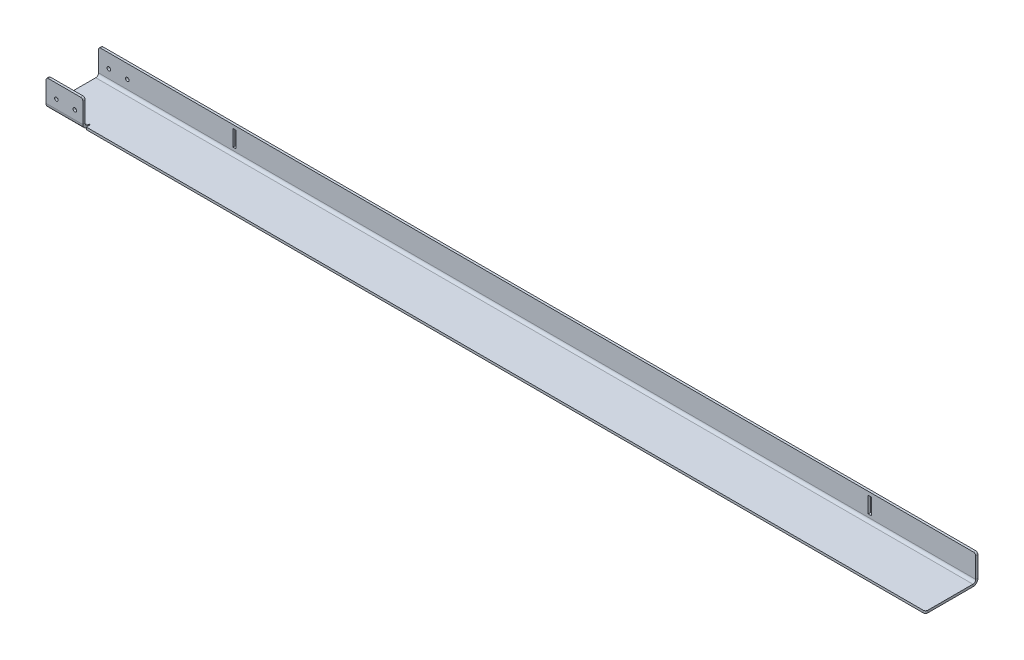
SolidWorks part; units mm, degrees
note: The reader was unsure of these and kept them because the rebuilt part matched: flange length of "Edge-Flange1", "Edge-Flange2"; thickness of "Edge-Flange1", "Edge-Flange2".
material "5052-H32"
ref_plane "Front Plane" through (0, 0, 0) normal (0, 0, 1) x (1, 0, 0)
ref_plane "Top Plane" through (0, 0, 0) normal (0, 1, 0) x (1, 0, 0)
ref_plane "Right Plane" through (0, 0, 0) normal (1, 0, 0) x (0, 0, -1)
sketch "Sketch1" plane through (0, 0, 0) normal (0, 1, 0) x (1, 0, 0)
  line L5 (-604.8375, -72.39) -> (604.8375, -72.39)
  line L6 (-604.8375, -72.39) -> (-604.8375, 0)
  line L7 (-604.8375, 0) -> (604.8375, 0)
  line L8 (604.8375, -72.39) -> (604.8375, 0)
  point P4 (0, 0)
  dimension "D1" = 1209.675
  dimension "D2" = 72.39
base flange "Base-Flange1" sketch "Sketch1" thickness 3.175 reverse thickness direction yes parameters "D1"=3.81
edge flange "Edge-Flange1" sketch "Sketch8" flange angle 90 flange length 38.1 flange position material inside bend radius 3.81 thickness 3.175 relief rectangular parameters "D6"=10
sketch "Sketch8" plane through (0, 3.175, 0) normal (0, 0, -1) x (-1, 0, 0)
  line L2 (604.8375, 0) -> (604.8375, 34.925)
  line L3 (604.8375, 34.925) -> (-604.8375, 34.925)
  line L4 (-604.8375, 34.925) -> (-604.8375, 0)
  line L7 (-604.8375, 0) -> (604.8375, 0) construction
  line L8 (-604.8375, 0) -> (604.8375, 0)
bend "EdgeBend1" bend radius 3.81 bend angle 90 parameters "D5"=1
sketch "Sketch9" plane through (0, 0, 0) normal (0, -1, 0) x (-1, 0, 0)
  line L0 (-604.8375, -72.39) -> (-604.8375, -6.985) construction
  line L2 (-604.8375, 0) -> (604.8375, 0) construction
  circle A0 centre (-364.3313, -38.1) radius 21.717
  circle A2 centre (116.6787, -38.1) radius 21.717
  dimension "D1" = 38.1
  dimension "D4" = 43.434
  dimension "D2" = 240.5062
  dimension "D3" = 481.01
extrude "Cut-Extrude1" [suppressed] cut sketch "Sketch9" against normal through all
sketch "Sketch10" plane through (0, 0, 0) normal (0, 0, -1) x (-1, 0, 0)
  line L0 (604.8375, 6.985) -> (604.8375, 38.1) construction
  line L1 (415.3535, 33.3375) -> (419.5445, 33.3375)
  line L2 (415.3535, 33.3375) -> (415.3535, 11.1125)
  line L3 (415.3535, 11.1125) -> (419.5445, 11.1125)
  line L4 (419.5445, 33.3375) -> (419.5445, 11.1125)
  line L5 (604.8375, 38.1) -> (-604.8375, 38.1) construction
  dimension "D1" = 185.293
  dimension "D2" = 4.191
  dimension "D3" = 22.225
  dimension "D4" = 4.7625
extrude "Cut-Extrude2" cut sketch "Sketch10" against normal through all normal cut yes
edge flange "Edge-Flange2" sketch "Sketch15" flange angle 90 flange length 38.1 flange position material outside bend radius 3.81 thickness 3.175 relief rectangular parameters "D6"=10
sketch "Sketch15" plane through (0, 3.175, 72.39) normal (0, 0, -1) x (-1, 0, 0)
  line L3 (554.0375, 34.925) -> (604.8375, 34.925)
  line L4 (604.8375, 34.925) -> (604.8375, 0)
  line L5 (604.8375, 0) -> (-604.8375, 0) construction
  line L6 (604.8375, 0) -> (554.0375, 0)
  line L7 (554.0375, 34.925) -> (554.0375, 0)
  dimension "D1" = 50.8
bend "EdgeBend2" bend radius 3.81 bend angle 90 parameters "D5"=2
hole_wizard "#10 (0.1935) Diameter Hole1" positions "Sketch16" profile "Sketch17" hole size "#10" standard "ANSI Inch" end condition through all
sketch "Sketch16" plane through (0, 0, 75.565) normal (0, 0, 1) x (1, 0, 0)
  line L0 (-554.0375, 0) -> (-604.8375, 0) construction
  line L1 (-554.0375, 38.1) -> (-554.0375, 6.985) construction
  point P0 (-565.15, 19.05)
  point P2 (-590.55, 19.05)
  dimension "D1" = 19.05
  dimension "D2" = 11.1125
  dimension "D3" = 25.4
sketch "Sketch17" plane through (-565.15, 19.05, 75.565) normal (1, 0, 0) x (0, -1, 0)
  line L0 (0, 0) -> (0, 75.565)
  line L1 (0, 75.565) -> (2.4574, 75.565)
  line L2 (2.4574, 75.565) -> (2.4574, 0)
  line L5 (2.4574, 0) -> (0, 0)
  line L11 (0, -6.35) -> (0, 107.95) construction
  dimension "Thru Hole Dia." = 4.9149
  dimension "Thru Hole Depth" = 75.565
fillet "Fillet1" radius 3.175 5 edges at (604.8375, 38.1, 1.5875) (604.8375, 1.5875, 72.39) (-604.8375, 38.1, 1.5875) (-604.8375, 38.1, 73.9775) (-554.0375, 38.1, 73.9775)
pattern_linear "LPattern1" count 2 spacing 876.173 along (1, 0, 0) of "Cut-Extrude2"
sketch "Bend-Lines1" [suppressed] plane through (0, 0, 0) normal (0, 1, 0) x (1, 0, 0)
sketch "Bounding-Box1" [suppressed] plane through (0, 0, 0) normal (0, 1, 0) x (1, 0, 0)
sheet metal parameters "Sheet-Metal1" thickness 3.175 parameters "D1"=3
flat pattern "Flat-Pattern1" [suppressed]
sketch "Bend-Lines2" plane through (0, 0, 0) normal (0, 1, 0) x (1, 0, 0)
sketch3d "Bounding-Box2" [suppressed]
  line L0 (-631.825, 0, 0) -> (631.825, 0, 0) construction
  line L1 (-631.825, -101.6, 0) -> (631.825, -101.6, 0) construction
  line L2 (-631.825, 0, 0) -> (-631.825, -101.6, 0) construction
  line L3 (631.825, 0, 0) -> (631.825, -101.6, 0) construction
sheet metal parameters "Sheet-Metal2" thickness 3.175 parameters "D1"=3, "D7"=3
flat pattern "Flat-Pattern1"
sketch "Bend-Lines2" plane through (0, 0, 0) normal (0, 1, 0) x (1, 0, 0)
  line L0 (631.825, -2.4657) -> (-631.825, -2.4657) construction
  line L1 (631.825, -2.4657) -> (-631.825, -2.4657) construction
sketch3d "Bounding-Box2" [suppressed]
  line L0 (631.825, 33.1686, 0) -> (-631.825, 33.1686, 0) construction
  line L1 (631.825, -101.6, 0) -> (-631.825, -101.6, 0) construction
  line L2 (631.825, 33.1686, 0) -> (631.825, -101.6, 0) construction
  line L3 (-631.825, 33.1686, 0) -> (-631.825, -101.6, 0) construction
bend of the flat pattern "Flatten-<EdgeBend1>1"
sheet metal parameters "Sheet-Metal3" thickness 3.175 parameters "D1"=3, "D7"=3
flat pattern "Flat-Pattern1"
sketch "Bend-Lines2" plane through (0, 0, 0) normal (0, -1, 0) x (-1, 0, 0)
  line L0 (631.825, -2.4657) -> (-631.825, -2.4657) construction
  line L1 (631.825, -2.4657) -> (-631.825, -2.4657) construction
sketch3d "Bounding-Box2" [suppressed]
  line L0 (-631.825, 33.1686, 0) -> (631.825, 33.1686, 0) construction
  line L1 (-631.825, -101.6, 0) -> (631.825, -101.6, 0) construction
  line L2 (-631.825, 33.1686, 0) -> (-631.825, -101.6, 0) construction
  line L3 (631.825, 33.1686, 0) -> (631.825, -101.6, 0) construction
bend of the flat pattern "Flatten-<EdgeBend1>1"
sheet metal parameters "Sheet-Metal4" thickness 3.175 parameters "D1"=3, "D7"=3
flat pattern "Flat-Pattern1"
sketch "Bend-Lines2" plane through (0, 0, 0) normal (0, -1, 0) x (-1, 0, 0)
  line L0 (631.825, -2.4657) -> (-631.825, -2.4657) construction
  line L1 (631.825, -2.4657) -> (-631.825, -2.4657) construction
sketch3d "Bounding-Box2" [suppressed]
  line L0 (-631.825, 33.1686, 0) -> (631.825, 33.1686, 0) construction
  line L1 (-631.825, -101.6, 0) -> (631.825, -101.6, 0) construction
  line L2 (-631.825, 33.1686, 0) -> (-631.825, -101.6, 0) construction
  line L3 (631.825, 33.1686, 0) -> (631.825, -101.6, 0) construction
bend of the flat pattern "Flatten-<EdgeBend1>1"
sheet metal parameters "Sheet-Metal6" thickness 3.175 parameters "D1"=3, "D7"=3
flat pattern "Flat-Pattern1"
sketch "Bend-Lines2" plane through (0, 0, 0) normal (0, -1, 0) x (-1, 0, 0)
  line L0 (631.825, -2.7458) -> (-631.825, -2.7458) construction
  line L1 (631.825, -2.7458) -> (-631.825, -2.7458) construction
  line L2 (581.025, -73.628) -> (631.825, -73.628) construction
  line L3 (581.025, -73.628) -> (631.825, -73.628) construction
sketch3d "Bounding-Box2" [suppressed]
  line L0 (-631.825, 32.6084, 0) -> (631.825, 32.6084, 0) construction
  line L1 (-631.825, -109.156, 0) -> (631.825, -109.156, 0) construction
  line L2 (-631.825, 32.6084, 0) -> (-631.825, -109.156, 0) construction
  line L3 (631.825, 32.6084, 0) -> (631.825, -109.156, 0) construction
bend of the flat pattern "Flatten-<EdgeBend1>1"
bend of the flat pattern "Flatten-<EdgeBend2>1"
sheet metal parameters "Sheet-Metal7" thickness 3.175 parameters "D1"=3, "D7"=3
flat pattern "Flat-Pattern1"
sketch "Bend-Lines2" plane through (0, 0, 0) normal (0, -1, 0) x (-1, 0, 0)
  line L0 (617.5375, -2.7458) -> (-617.5375, -2.7458) construction
  line L1 (617.5375, -2.7458) -> (-617.5375, -2.7458) construction
  line L2 (566.7375, -73.4542) -> (617.5375, -73.4542) construction
  line L3 (566.7375, -73.4542) -> (617.5375, -73.4542) construction
sketch3d "Bounding-Box2" [suppressed]
  line L0 (617.5375, 32.6068, 0) -> (-617.5375, 32.6084, 0) construction
  line L1 (617.5373, -108.8084, 0) -> (-617.5377, -108.8068, 0) construction
  line L2 (617.5375, 32.6068, 0) -> (617.5373, -108.8084, 0) construction
  line L3 (-617.5375, 32.6084, 0) -> (-617.5377, -108.8068, 0) construction
bend of the flat pattern "Flatten-<EdgeBend1>1"
bend of the flat pattern "Flatten-<EdgeBend2>1"
sheet metal parameters "Sheet-Metal8" thickness 3.175 parameters "D1"=3, "D7"=3
flat pattern "Flat-Pattern1"
sketch "Bend-Lines2" plane through (0, 0, 0) normal (0, -1, 0) x (-1, 0, 0)
  line L0 (604.8375, -2.6797) -> (-604.8375, -2.6797) construction
  line L1 (604.8375, -2.6797) -> (-604.8375, -2.6797) construction
  line L2 (554.0375, -72.8853) -> (604.8375, -72.8853) construction
  line L3 (554.0375, -72.8853) -> (604.8375, -72.8853) construction
sketch3d "Bounding-Box2" [suppressed]
  line L0 (604.8375, 32.7391, 0) -> (-604.8375, 32.7406, 0) construction
  line L1 (604.8373, -108.3056, 0) -> (-604.8377, -108.3041, 0) construction
  line L2 (604.8375, 32.7391, 0) -> (604.8373, -108.3056, 0) construction
  line L3 (-604.8375, 32.7406, 0) -> (-604.8377, -108.3041, 0) construction
bend of the flat pattern "Flatten-<EdgeBend1>1"
bend of the flat pattern "Flatten-<EdgeBend2>1"
